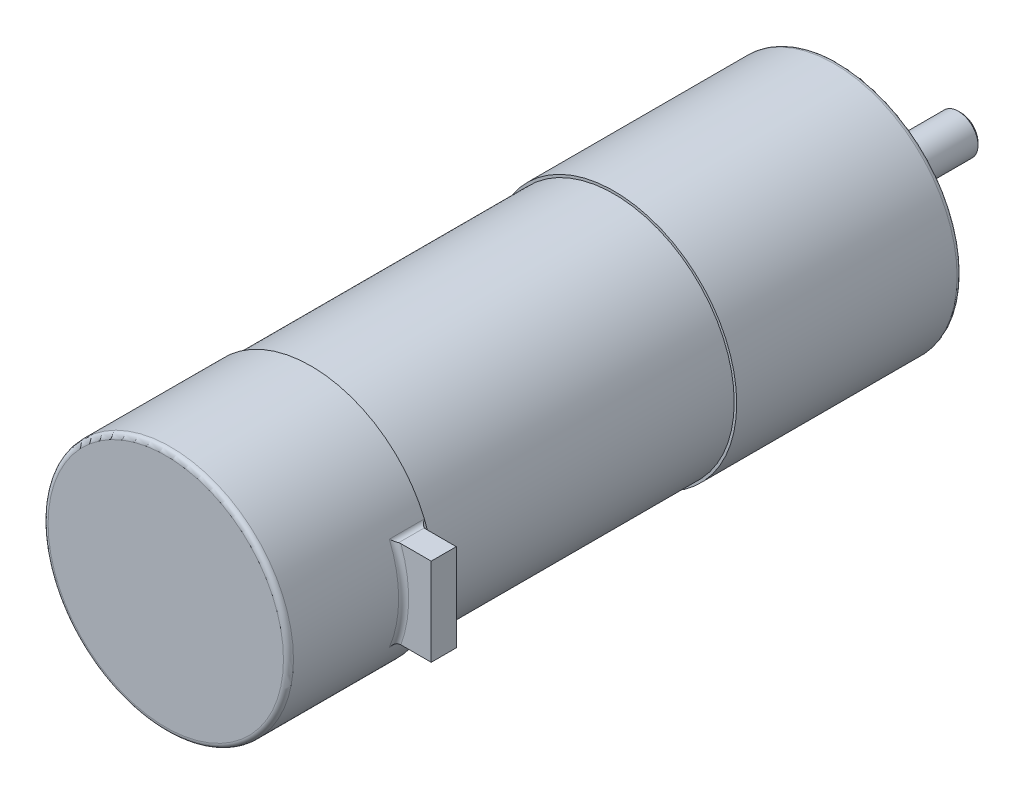
SolidWorks part; units mm, degrees
material "6061-T6 (SS)"
ref_plane "Front Plane" through (0, 0, 0) normal (0, 0, 1) x (1, 0, 0)
ref_plane "Top Plane" through (0, 0, 0) normal (0, 1, 0) x (1, 0, 0)
ref_plane "Right Plane" through (0, 0, 0) normal (1, 0, 0) x (0, 0, -1)
sketch "Sketch1" plane through (0, 0, 0) normal (0, 0, 1) x (1, 0, 0)
  circle A0 centre (0, 0) radius 12.446
  dimension "D1" = 24.892
extrude "Boss-Extrude1" add sketch "Sketch1" along normal blind 22.86
sketch "Sketch2" plane through (0, 0, 22.86) normal (0, 0, 1) x (1, 0, 0)
  circle A0 centre (0, 0) radius 12.192
  dimension "D1" = 24.384
extrude "Boss-Extrude2" add sketch "Sketch2" along normal blind 30.734
sketch "Sketch3" plane through (0, 0, 53.594) normal (0, 0, 1) x (1, 0, 0)
  circle A0 centre (0, 0) radius 12.446
  dimension "D1" = 24.892
extrude "Boss-Extrude3" add sketch "Sketch3" along normal blind 14.732
sketch "Sketch4" plane through (0, 0, 0) normal (0, 0, -1) x (-1, 0, 0)
  circle A0 centre (0, 0) radius 3.5179
  dimension "D1" = 7.0358
extrude "Boss-Extrude4" add sketch "Sketch4" along normal blind 2.794
sketch "Sketch5" plane through (0, 0, 0) normal (0, 0, -1) x (-1, 0, 0)
  circle A0 centre (0, 0) radius 1.9939
  dimension "D1" = 3.9878
extrude "Boss-Extrude5" add sketch "Sketch5" along normal blind 12.319
chamfer "Chamfer1" distance 0.254 angle 45 1 edges at (-1.9939, 0, -12.319)
fillet "Fillet1" radius 0.635 1 edges at (-3.5179, 0, -2.794)
fillet "Fillet2" radius 0.254 1 edges at (-3.5179, 0, 0)
fillet "Fillet3" radius 0.508 2 edges at (12.446, 0, 68.326) (12.446, 0, 0)
sketch "Sketch6" plane through (0, 0, 0) normal (0, 0, -1) x (-1, 0, 0)
  line L0 (0, 0) -> (0, 12.446) construction
  line L1 (-8.6995, 0) -> (0, 0) construction
  circle A0 centre (-8.6995, 0) radius 1.5
  circle A1 centre (0, 0) radius 12.446 construction
  circle A2 centre (8.6995, 0) radius 1.5
  dimension "D1" = 3
  dimension "D2" = 17.399
extrude "Cut-Extrude1" cut sketch "Sketch6" against normal blind 7.62
sketch "Sketch7" plane through (0, 0, 0) normal (1, 0, 0) x (0, -1, 0)
  line L0 (-4.445, -54.102) -> (4.445, -54.102)
  line L1 (4.445, -54.102) -> (4.445, -56.642)
  line L2 (4.445, -56.642) -> (-4.445, -56.642)
  line L3 (-4.445, -56.642) -> (-4.445, -54.102)
  line L4 (0, -68.326) -> (0, 49931.674) construction
  line L5 (-11.938, -68.326) -> (11.938, -68.326) construction
  line L6 (12.446, -53.594) -> (-12.446, -53.594) construction
  point P5 (0, -54.102)
  point P11 (0, -68.326)
  dimension "D1" = 8.89
  dimension "D2" = 2.54
  dimension "D3" = 0.508
extrude "Boss-Extrude6" add sketch "Sketch7" along normal blind 15.24
fillet "Fillet4" radius 0.508 4 edges at (11.6252, -4.445, 55.372) (12.446, 0, 54.102) (11.6252, 4.445, 55.372) (12.446, 0, 56.642)
